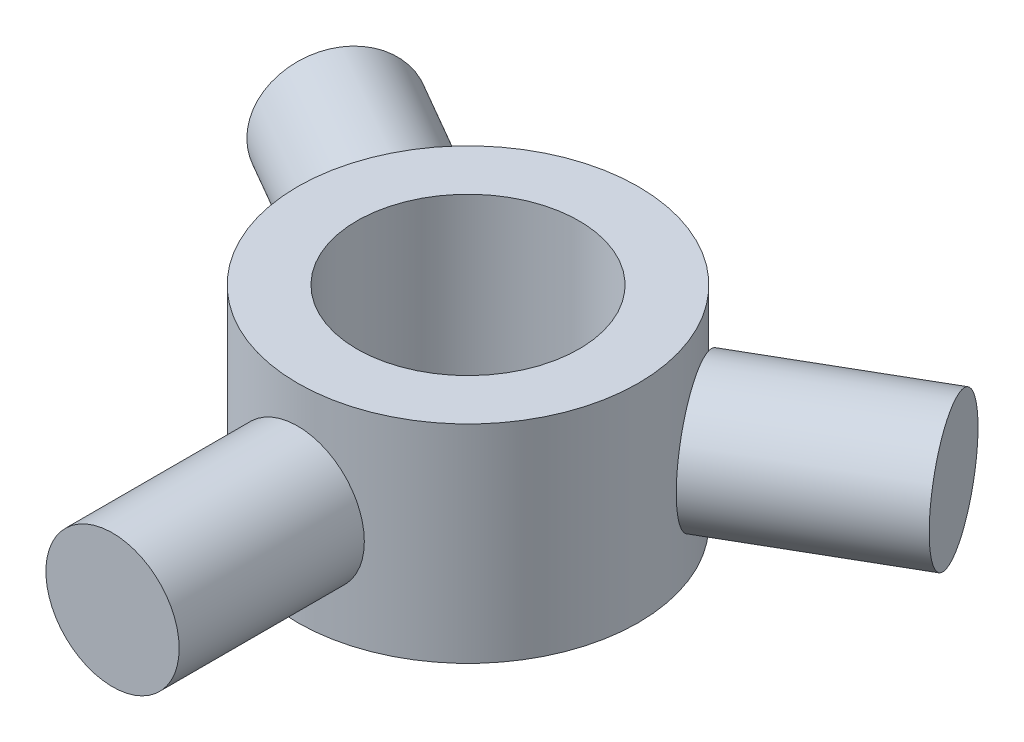
SolidWorks part; units mm, degrees
material "Acier non allié"
ref_plane "Plan de face" through (0, 0, 0) normal (0, 0, 1) x (1, 0, 0)
ref_plane "Plan de dessus" through (0, 0, 0) normal (0, 1, 0) x (1, 0, 0)
ref_plane "Plan de droite" through (0, 0, 0) normal (1, 0, 0) x (0, 0, -1)
sketch "Esquisse1" plane through (0, 0, 0) normal (0, 1, 0) x (1, 0, 0)
  circle A0 centre (0, 0) radius 23
  circle A1 centre (0, 0) radius 15
  dimension "D1" = 46
  dimension "D2" = 30
extrude "Boss.-Extru.1" add sketch "Esquisse1" along normal blind 14 and the other way blind 14
ref_plane "Plan1" through (0, 0, 23) normal (0, 0, 1) x (1, 0, 0)
sketch "Esquisse2" plane through (0, 0, 23) normal (0, 0, 1) x (1, 0, 0)
  circle A0 centre (0, 0) radius 9
  dimension "D1" = 18
extrude "Boss.-Extru.2" add sketch "Esquisse2" along normal blind 25 separate body contours A0
pattern_circular "Répétition circulaire6" count 3 every 120 about axis through (0, -14, 0) along (0, 1, 0) of bodies 102
